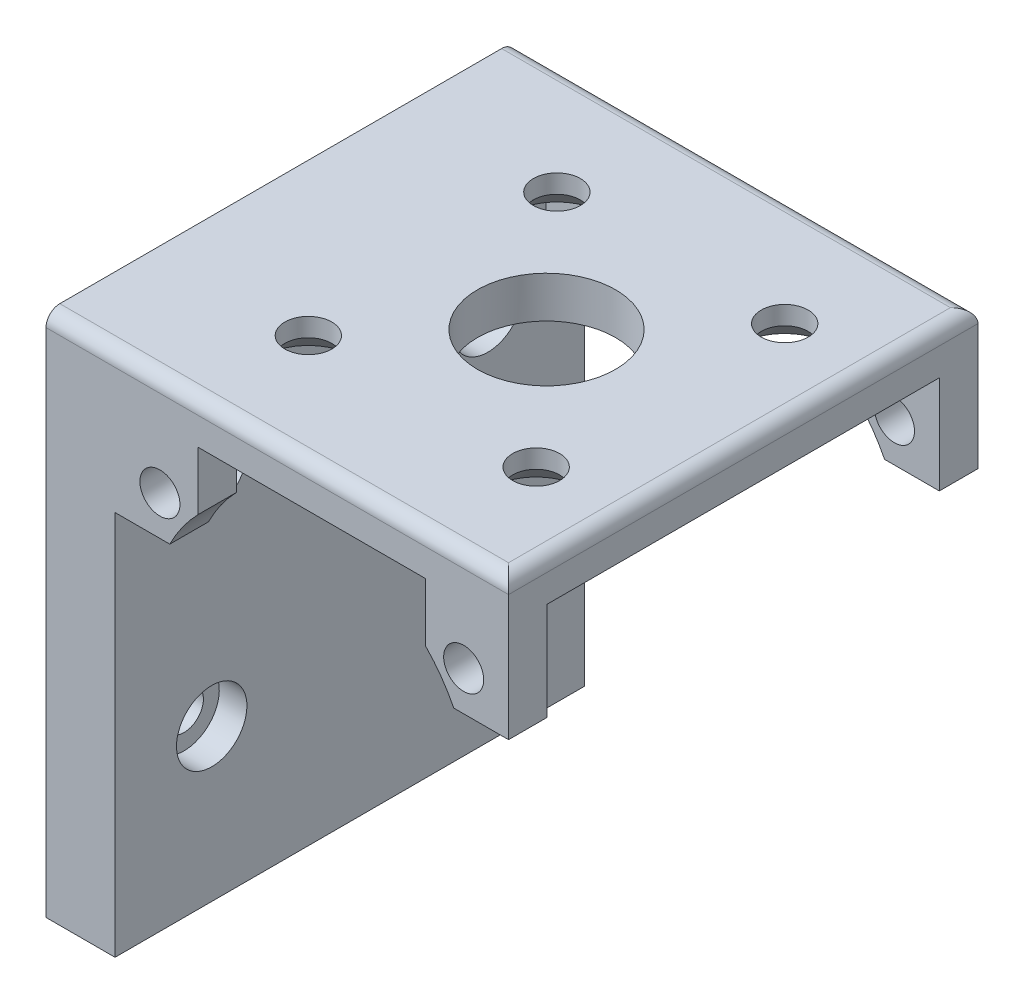
SolidWorks part; units mm, degrees
ref_plane "Front Plane" through (0, 0, 0) normal (0, 0, 1) x (1, 0, 0)
ref_plane "Top Plane" through (0, 0, 0) normal (0, 1, 0) x (1, 0, 0)
ref_plane "Right Plane" through (0, 0, 0) normal (1, 0, 0) x (0, 0, -1)
sketch "Sketch1" plane through (0, 0, 0) normal (0, 0, 1) x (1, 0, 0)
  line L0 (0, 0) -> (0, 5.0753) construction
  line L1 (-14.25, 11.25) -> (14.25, 11.25)
  line L2 (-14.25, 11.25) -> (-14.25, -35.25)
  line L3 (-14.25, -35.25) -> (14.25, -35.25)
  line L4 (14.25, 11.25) -> (14.25, -35.25)
  line L5 (-14.25, 11.25) -> (-7.75, 11.25)
  line L6 (-14.25, 11.25) -> (-14.25, 4.75)
  line L7 (-14.25, 4.75) -> (-7.75, 4.75)
  line L8 (-7.75, 11.25) -> (-7.75, 4.75)
  line L9 (0, 0) -> (3.7441, 0) construction
  line L10 (14.25, 4.75) -> (7.75, 4.75)
  line L11 (7.75, 11.25) -> (7.75, 4.75)
  line L12 (-14.25, -12) -> (23.601, -12) construction
  line L13 (7.75, -35.25) -> (7.75, -29.75)
  line L14 (14.25, -28.75) -> (8.75, -28.75)
  line L15 (-7.75, -35.25) -> (-7.75, -29.75)
  line L16 (-14.25, -28.75) -> (-8.75, -28.75)
  line L18 (14.25, 11.25) -> (-14.25, 11.25)
  line L19 (14.25, 11.25) -> (14.25, 15.25)
  line L20 (14.25, 15.25) -> (-14.25, 15.25)
  line L21 (-14.25, 11.25) -> (-14.25, 15.25)
  line L22 (-14.25, 4.75) -> (-16.25, 4.75)
  line L23 (-14.25, 4.75) -> (-14.25, 15.25)
  line L24 (-14.25, 15.25) -> (-16.25, 15.25)
  line L25 (-16.25, 4.75) -> (-16.25, 15.25)
  line L26 (14.25, 15.25) -> (16.25, 15.25)
  line L27 (14.25, 15.25) -> (14.25, 4.75)
  line L28 (14.25, 4.75) -> (16.25, 4.75)
  line L29 (16.25, 15.25) -> (16.25, 4.75)
  line L30 (-8.25, 11.25) -> (8.25, 11.25)
  line L31 (-8.25, 11.25) -> (-8.25, 4.75)
  line L32 (-8.25, 4.75) -> (8.25, 4.75)
  line L33 (8.25, 11.25) -> (8.25, 4.75)
  line L34 (-8.25, 11.25) -> (8.25, 11.25)
  line L35 (-8.25, 11.25) -> (-8.25, 12.25)
  line L36 (-8.25, 12.25) -> (8.25, 12.25)
  line L37 (8.25, 11.25) -> (8.25, 12.25)
  circle A1 centre (0, 0) radius 10.45
  circle A2 centre (-11, 8) radius 1.45
  circle A3 centre (11, 8) radius 1.45
  circle A4 centre (11, -32) radius 1.45
  circle A5 centre (-11, -32) radius 1.45
  arc A7 (-7.75, -29.75) -> (-8.75, -28.75) centre (-8.75, -29.75) ccw
  arc A8 (8.75, -28.75) -> (7.75, -29.75) centre (8.75, -29.75) ccw
  circle A9 centre (0, 0) radius 11.5
  point P0 (0, 0)
  point P35 (-7.75, -28.75)
  point P38 (7.75, -28.75)
  dimension "D1" = 28.5
  dimension "D2" = 46.5
  dimension "D3" = 23
  dimension "D4" = 11.25
  dimension "D5" = 2.9
  dimension "D6" = 3.25
  dimension "D7" = 3.25
  dimension "D10" = 3.25
  dimension "D12" = 1
  dimension "D16" = 20.9
  dimension "D17" = 0.5
  dimension "D11" = 3.25
  dimension "D13" = 4
  dimension "D14" = 2
  dimension "D15" = 2
  dimension "D18" = 0.5
  dimension "D19" = 1
  dimension "D8" = 2
  dimension "D9" = 2
extrude "Boss-Extrude7" add sketch "Sketch1" along normal blind 17 and the other way blind 17 contours L37 L18 L19 L20 L21 L1 L35 L36 | A9 L10 L4 L18 L33 A3 | A9 L31 L1 L2 L7 A2 region at (0, 13.5038, 0) region at (-11.25, 11.1615, 0) region at (14.1615, 8, 0)
sketch "Sketch34" plane through (-14.25, 0, 0) normal (-1, 0, 0) x (0, 0, 1)
  line L0 (-17, 4.75) -> (17, 4.75) construction
  line L1 (-14.2, 12.25) -> (14.2, 12.25)
  line L2 (-14.2, 12.25) -> (-14.2, 4.75)
  line L3 (-14.2, 4.75) -> (14.2, 4.75)
  line L4 (14.2, 12.25) -> (14.2, 4.75)
  line L5 (-17, 4.75) -> (-17, 15.25) construction
  line L6 (17, 4.75) -> (17, 15.25) construction
  line L7 (-17, 15.25) -> (17, 15.25) construction
  dimension "D1" = 2.8
  dimension "D2" = 2.8
  dimension "D3" = 3
extrude "Cut-Extrude11" cut sketch "Sketch34" against normal through all
sketch "Sketch35" plane through (0, 15.25, 0) normal (0, 1, 0) x (1, 0, 0)
  circle A0 centre (0, 0) radius 5
extrude "Cut-Extrude12" cut sketch "Sketch35" against normal through all
sketch "Sketch39" plane through (0, 12.25, 0) normal (0, -1, 0) x (1, 0, 0)
  line L0 (-14.25, 14.2) -> (-14.25, -14.2) construction
  line L1 (-8.25, 17) -> (8.25, 17) construction
  line L3 (0, 0) -> (0, 7.1623) construction
  line L4 (0, 0) -> (6.1391, 0) construction
  circle A0 centre (-8.25, 9) radius 1.5
  circle A1 centre (8.25, 9) radius 1.5
  circle A2 centre (-8.25, -9) radius 1.5
  circle A3 centre (8.25, -9) radius 1.5
  point P0 (-8.25, 9)
  point P9 (8.25, 9)
  point P12 (-8.25, -9)
  point P14 (8.25, -9)
  dimension "D1" = 6
  dimension "D2" = 8
hole_wizard "CSK for M3 Hex Socket Countersunk Cap Screw3" positions "Sketch39" profile "Sketch40" countersink size "M3" standard "ISO" end condition through all
sketch "Sketch40" plane through (-8.25, 12.25, 9) normal (1, 0, 0) x (0, 0, -1)
  line L0 (0, 0) -> (0, 3)
  line L1 (0, 3) -> (1.7, 3)
  line L2 (1.7, 3) -> (1.7, 1.66)
  line L3 (1.7, 1.66) -> (3.36, 0)
  line L5 (3.36, 0) -> (0, 0)
  line L6 (-1.7, 1.66) -> (-3.36, 0) construction
  line L11 (0, -6.35) -> (0, 107.95) construction
  dimension "Thru Hole Dia." = 3.4
  dimension "Thru Hole Depth" = 3
  dimension "Near C'Sink Dia." = 6.72
  dimension "Near C'Sink Angle" = 90
fillet "Fillet5" radius 1 3 edges at (14.25, 15.25, 0) (0, 15.25, -17) (0, 15.25, 17)
sketch "Sketch41" plane through (0, 0, 17) normal (0, 0, 1) x (1, 0, 0)
  line L0 (14.25, 4.75) -> (14.25, 14.25) construction
  line L1 (-14.25, 4.75) -> (14.25, 4.75)
  line L2 (-14.25, 4.75) -> (-14.25, 5.15)
  line L3 (-14.25, 5.15) -> (14.25, 5.15)
  line L4 (14.25, 4.75) -> (14.25, 5.15)
  dimension "D1" = 0.4
extrude "Cut-Extrude13" cut sketch "Sketch41" against normal through all
sketch "Sketch45" plane through (0, 0, 17) normal (0, 0, 1) x (1, 0, 0)
  circle A0 centre (11, 8) radius 1.45
  circle A1 centre (0, 0) radius 11.5
sketch "Sketch46" plane through (-14.25, 0, 0) normal (-1, 0, 0) x (0, 0, 1)
  line L1 (16, 15.25) -> (17, 15.25)
  line L4 (17, 15.25) -> (17, 14.25)
  line L5 (17, 15.25) -> (-17, 15.25)
  line L6 (17, 15.25) -> (17, -22.75)
  line L7 (17, -22.75) -> (-17, -22.75)
  line L8 (-17, 15.25) -> (-17, -22.75)
  line M3 (-17, 14.25) -> (-17, 5.15)
  line M4 (-17, 5.15) -> (-14.2, 5.15)
  line M5 (-14.2, 5.15) -> (-14.2, 12.25)
  line M6 (-14.2, 12.25) -> (14.2, 12.25)
  line M7 (14.2, 12.25) -> (14.2, 5.15)
  line M8 (14.2, 5.15) -> (17, 5.15)
  line M9 (17, 5.15) -> (17, 14.25)
  arc M10 (17, 14.25) -> (16, 15.25) centre (16, 14.25) ccw
  line M11 (16, 15.25) -> (-16, 15.25)
  arc M12 (-16, 15.25) -> (-17, 14.25) centre (-16, 14.25) ccw
  dimension "D1" = 34
  dimension "D2" = 38
extrude "Boss-Extrude8" add sketch "Sketch46" along normal blind 5 contours L8 L7 L6 M4 M8 M7 M6 M5 | M12 M3 M4 M5 M6 M7 M8 M9 M10 M11 region at (-14.25, 12.3254, 0) region at (-14.25, -5.7322, 0)
sketch "Sketch48" plane through (-19.25, 0, 0) normal (-1, 0, 0) x (0, 0, 1)
  line L0 (17, -22.75) -> (-17, -22.75) construction
  line L1 (-17, 14.25) -> (-17, -22.75) construction
  circle A0 centre (-10, -11.75) radius 1.4
  circle A1 centre (10, -11.75) radius 1.4
  circle A2 centre (10, 4.25) radius 1.4
  circle A3 centre (-10, 4.25) radius 1.4
  dimension "D1" = 11
  dimension "D2" = 7
  dimension "D5" = 27
  dimension "D6" = 20
  dimension "D7" = 16
  dimension "D3" = 2
  dimension "D4" = 2
extrude "Cut-Extrude14" cut sketch "Sketch48" against normal blind 5
sketch "Sketch49" plane through (-14.25, 0, 0) normal (1, 0, 0) x (0, 0, -1)
  line L0 (-17, -22.75) -> (17, -22.75) construction
  line L1 (-17, 5.15) -> (-17, -22.75) construction
  circle A1 centre (-10, -11.75) radius 2.55
  circle A2 centre (10, -11.75) radius 2.55
  circle A3 centre (10, 4.25) radius 2.55
  circle A4 centre (-10, 4.25) radius 2.55
  dimension "D1" = 5.1
  dimension "D2" = 11
  dimension "D3" = 7
  dimension "D4" = 2
  dimension "D5" = 2
extrude "Cut-Extrude15" cut sketch "Sketch49" against normal blind 2
